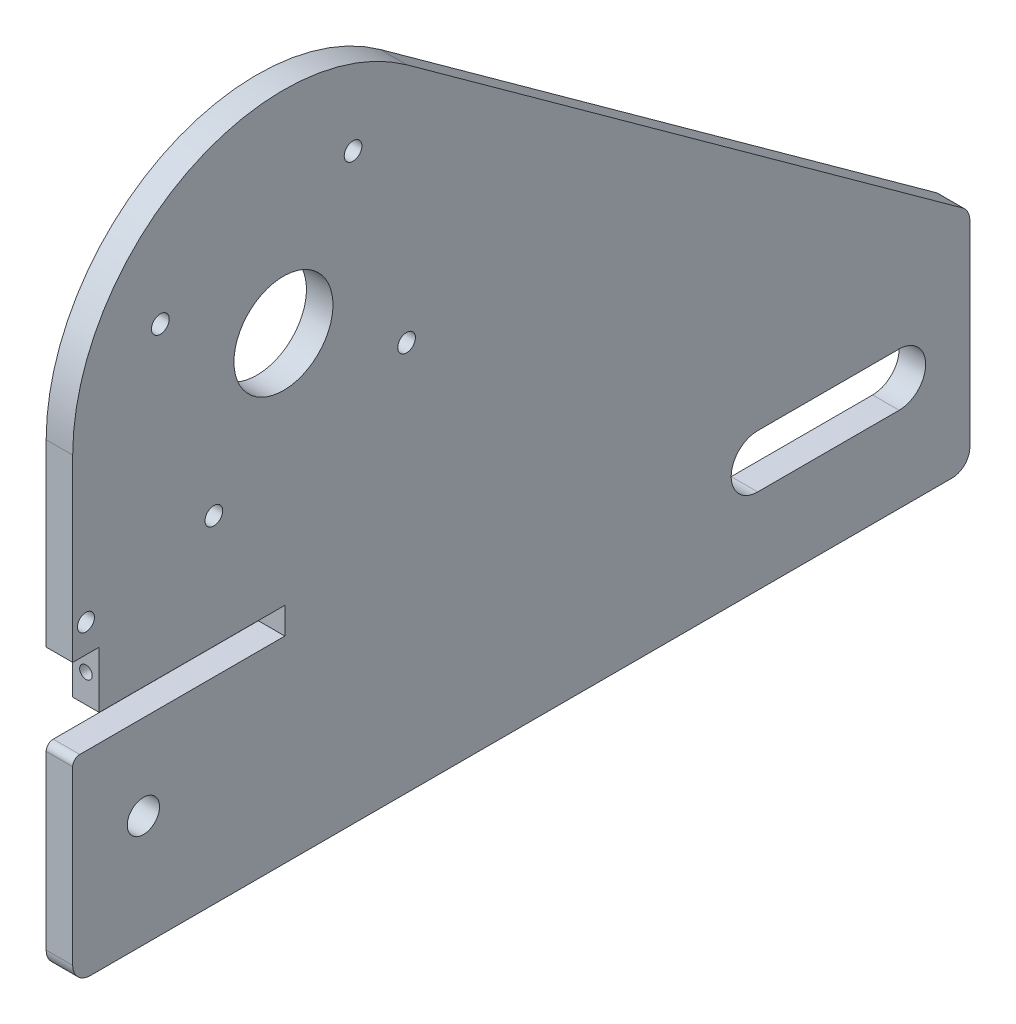
SolidWorks part; units mm, degrees
ref_plane "Front Plane" through (0, 0, 0) normal (0, 0, 1) x (1, 0, 0)
ref_plane "Top Plane" through (0, 0, 0) normal (0, 1, 0) x (1, 0, 0)
ref_plane "Right Plane" through (0, 0, 0) normal (1, 0, 0) x (0, 0, -1)
sketch "Sketch1" plane through (0, 0, 0) normal (1, 0, 0) x (0, 0, -1)
  line L0 (-77.3828, 0) -> (77.3828, 0)
  line L1 (80.5578, 3.175) -> (80.5578, 38.5097)
  line L2 (-80.5578, 82.55) -> (-80.5578, 50.292)
  line L3 (79.2431, 41.0826) -> (-20.5306, 113.2224)
  line L4 (-75.7953, 50.292) -> (-75.7953, 40.132)
  line L5 (-80.5578, 50.292) -> (-75.7953, 50.292)
  line L6 (67.8578, 20.066) -> (42.4578, 20.066) construction
  line L7 (-75.7953, 40.132) -> (-42.4578, 40.132)
  line L8 (-42.4578, 40.132) -> (-42.4578, 35.3441)
  line L9 (-42.4578, 35.3441) -> (-79.2878, 35.3441)
  line L10 (-80.5578, 34.0741) -> (-80.5578, 3.175)
  line L11 (-38.3203, 96.7465) -> (80.2327, 60.1074) construction
  line L12 (-52.6061, 71.4678) -> (39.9396, -11.1914) construction
  line L13 (67.8578, 15.3035) -> (42.4578, 15.3035)
  line L14 (67.8578, 24.8285) -> (42.4578, 24.8285)
  arc A0 (67.8578, 15.3035) -> (67.8578, 24.8285) centre (67.8578, 20.066) ccw
  circle A1 centre (-42.7078, 82.55) radius 31.5 construction
  circle A2 centre (67.8578, 20.066) radius 76.2 construction
  circle A3 centre (67.8578, 20.066) radius 41.91 construction
  circle A4 centre (-42.7078, 82.55) radius 14.859 construction
  arc A5 (-20.5306, 113.2224) -> (-80.5578, 82.55) centre (-42.7078, 82.55) ccw
  arc A6 (-77.3828, 0) -> (-80.5578, 3.175) centre (-77.3828, 3.175) cw
  arc A7 (77.3828, 0) -> (80.5578, 3.175) centre (77.3828, 3.175) ccw
  arc A8 (80.5578, 38.5097) -> (79.2431, 41.0826) centre (77.3828, 38.5097) ccw
  arc A9 (-79.2878, 35.3441) -> (-80.5578, 34.0741) centre (-79.2878, 34.0741) ccw
  circle A10 centre (-55.209, 60.4394) radius 1.5875
  circle A11 centre (-67.8578, 20.066) radius 2.8956
  circle A12 centre (-20.5972, 70.0488) radius 1.5875
  circle A13 centre (-64.8184, 95.0512) radius 1.5875
  circle A14 centre (-30.2065, 104.6606) radius 1.5875
  circle A15 centre (-78.1765, 55.372) radius 1.524
  circle A16 centre (-42.7078, 82.55) radius 8.89
  arc A17 (42.4578, 24.8285) -> (42.4578, 15.3035) centre (42.4578, 20.066) ccw
  point P14 (0, 0)
  point P28 (80.5578, 40.132)
  point P39 (55.1578, 20.066)
  dimension "D4" = 9.525
  dimension "D7" = 29.718
  dimension "D8" = 63
  dimension "D9" = 6.35
  dimension "D12" = 3.175
  dimension "D13" = 1.27
  dimension "D14" = 83.82
  dimension "D15" = 152.4
  dimension "D18" = 5.7912
  dimension "D19" = 3.175
  dimension "D20" = 12.7
  dimension "D23" = 3.048
  dimension "D1" = 4.7879
  dimension "D2" = 40.132
  dimension "D3" = 20.066
  dimension "D5" = 12.7
  dimension "D6" = 38.1
  dimension "D10" = 127
  dimension "D11" = 82.55
  dimension "D17" = 25.4
  dimension "D21" = 4.7625
  dimension "D22" = 10.16
  dimension "D24" = 5.08
  dimension "D25" = 2.3813
  dimension "D26" = 25.4
  dimension "D16" = 4
extrude "Boss-Extrude1" add sketch "Sketch1" along normal blind 4.7625
sketch "Sketch2" plane through (0, 0, 75.7953) normal (0, 0, 1) x (1, 0, 0)
  line L0 (4.7625, 50.292) -> (4.7625, 40.132) construction
  line L1 (4.7625, 40.132) -> (0, 40.132) construction
  circle A0 centre (2.3813, 45.212) radius 1.1303
  point P4 (4.7625, 45.212)
  point P7 (2.3813, 40.132)
  dimension "D1" = 2.2606
extrude "Cut-Extrude1" cut sketch "Sketch2" against normal blind 6.35
